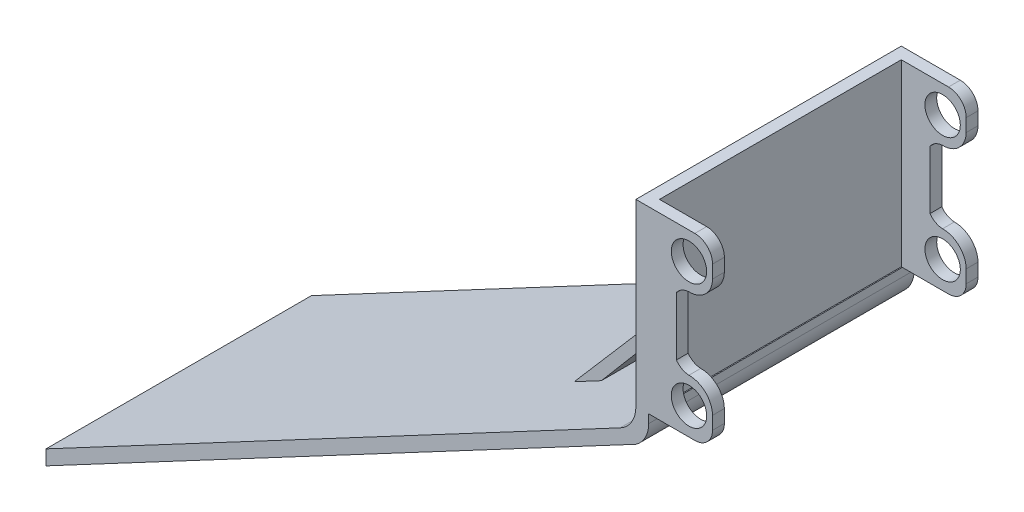
SolidWorks part; units mm, degrees
ref_plane "Plan de face" through (0, 0, 0) normal (0, 0, 1) x (1, 0, 0)
ref_plane "Plan de dessus" through (0, 0, 0) normal (0, 1, 0) x (1, 0, 0)
ref_plane "Plan de droite" through (0, 0, 0) normal (1, 0, 0) x (0, 0, -1)
sketch "Esquisse1" plane through (0, 0, 0) normal (1, 0, 0) x (0, 0, -1)
  line L0 (20.5, 0) -> (-20.5, 0)
  line L1 (-20.5, 0) -> (-20.5, -30.4)
  line L2 (-20.5, -30.4) -> (20.5, -30.4)
  line L3 (0, 9.6881) -> (0, -31.4707) construction
  line L4 (20.5, 0) -> (20.5, -30.4)
  point P8 (0, -30.4)
  point P9 (0, 0)
  dimension "D1" = 20.5
  dimension "D2" = 30.4
  dimension "D3" = 41
extrude "Boss.-Extru.1" add sketch "Esquisse1" along normal blind 2
sketch "Esquisse3" plane through (0, 0, 20.5) normal (0, 0, 1) x (1, 0, 0)
  line L0 (0, 0) -> (0, -30.4)
  line L1 (0, 0) -> (10, 0)
  line L2 (0, -30.4) -> (10, -30.4)
  line L3 (13, -3) -> (13, -5.196)
  line L4 (10, -15.2) -> (-32.1467, -15.2) construction
  line L5 (6.8684, -10.2502) -> (6.8684, -20.1498)
  line L6 (13, -25.204) -> (13, -27.4)
  circle A0 centre (9, -4.61) radius 3
  arc A1 (8.9893, -21.3235) -> (6.8684, -20.1498) centre (9.1338, -18.5593) cw
  arc A2 (13, -5.196) -> (8.9893, -9.0765) centre (9.0597, -5.1363) cw
  arc A3 (8.9893, -9.0765) -> (6.8684, -10.2502) centre (9.1338, -11.8407) ccw
  arc A4 (13, -25.204) -> (8.9893, -21.3235) centre (9.0597, -25.2637) ccw
  circle A5 centre (9, -25.79) radius 3
  arc A6 (10, 0) -> (13, -3) centre (10, -3) cw
  arc A7 (10, -30.4) -> (13, -27.4) centre (10, -27.4) ccw
  point P24 (13, 0)
  dimension "D3" = 6
  dimension "D4" = 3
  dimension "D6" = 4
  dimension "D2" = 3
  dimension "D5" = 4.61
  dimension "D1" = 13
extrude "Boss.-Extru.2" add sketch "Esquisse3" along normal blind 2
mirror "Symétrie1" about plane through (0, 0, 0) normal (0, 0, 1) of "Boss.-Extru.2"
sketch "Esquisse4" plane through (0, 0, 0) normal (-1, 0, 0) x (0, 0, 1)
  line L0 (-22.5, 0) -> (-22.5, -30.4) construction
  line L1 (-7.5, -7.5) -> (7.5, -7.5)
  line L2 (-7.5, -7.5) -> (-7.5, -22.9)
  line L3 (-7.5, -22.9) -> (7.5, -22.9)
  line L4 (7.5, -7.5) -> (7.5, -22.9)
  line L5 (22.5, 0) -> (22.5, -30.4) construction
  line L6 (-22.5, 0) -> (22.5, 0) construction
  line L7 (22.5, -30.4) -> (-22.5, -30.4) construction
  dimension "D1" = 15
  dimension "D2" = 15
  dimension "D3" = 7.5
  dimension "D4" = 7.5
extrude "Boss.-Extru.3" add sketch "Esquisse4" along normal blind 2.5
sketch "Esquisse11" plane through (0, 0, -22.5) normal (0, 0, -1) x (-1, 0, 0)
  line L0 (0, 0) -> (0, -30.4) construction
  line L1 (100, -86.6309) -> (100, -89.1309)
  line L4 (100, -89.1309) -> (0, -35.96)
  line L5 (0, -35.96) -> (0, -33.46)
  line L6 (0, -33.46) -> (100, -86.6309)
  point P2 (0, -35.96)
  dimension "D1" = 2.5
  dimension "D2" = 100
  dimension "D3" = 118
  dimension "D4" = 100
  dimension "D5" = 118
extrude "Boss.-Extru.9" add sketch "Esquisse11" against normal up to vertex (45 mm away) up to point (0, -30.4, 22.5)
sketch "Esquisse12" plane through (0, 0, -7.5) normal (0, 0, -1) x (-1, 0, 0)
  line L0 (2.5, -22.9) -> (20.8446, -44.5433)
  line L1 (100, -86.6309) -> (0, -33.46) construction
  line L2 (20.8446, -44.5433) -> (25.4455, -46.9896)
  line L3 (25.4455, -46.9896) -> (2.5, -20.4)
  line L4 (2.5, -7.5) -> (2.5, -22.9) construction
  line L5 (2.5, -20.4) -> (2.5, -22.9)
  point P5 (21.1988, -42.0685)
  dimension "D1" = 2.5
  dimension "D2" = 2.5
  dimension "D3" = 35.1213
  dimension "D4" = 139.207
extrude "Boss.-Extru.10" add sketch "Esquisse12" against normal up to vertex (15 mm away) up to point (-2.5, -22.9, 7.5)
sketch "Esquisse13" plane through (0, 0, -22.5) normal (0, 0, -1) x (-1, 0, 0)
  line L0 (0, -30.4) -> (0, -35.96)
  line L1 (0, -33.46) -> (0, -35.96) construction
  line L2 (0, -35.96) -> (-2.1725, -35.96)
  line L3 (-2.1725, -35.96) -> (-2.1725, -30.4)
  line L4 (0, -30.4) -> (-10, -30.4) construction
  line L5 (-2.1725, -30.4) -> (0, -30.4)
  line L11 (0, 0) -> (-10, 0)
  line L12 (-13, -3) -> (-13, -5.196)
  line L13 (-6.8684, -10.2502) -> (-6.8684, -20.1498)
  line L14 (-13, -25.204) -> (-13, -27.4)
  line L15 (-10, -30.4) -> (0, -30.4)
  line L16 (0, -30.4) -> (0, 0)
  line L17 (0, 0) -> (-10, 0)
  line L18 (-13, -3) -> (-13, -5.196)
  line L19 (-6.8684, -10.2502) -> (-6.8684, -20.1498)
  line L20 (-13, -25.204) -> (-13, -27.4)
  line L21 (-10, -30.4) -> (-2.1725, -30.4)
  arc A6 (-10, 0) -> (-13, -3) centre (-10, -3) ccw
  arc A7 (-13, -5.196) -> (-8.9893, -9.0765) centre (-9.0597, -5.1363) ccw
  arc A8 (-6.8684, -10.2502) -> (-8.9893, -9.0765) centre (-9.1338, -11.8407) ccw
  arc A9 (-8.9893, -21.3235) -> (-6.8684, -20.1498) centre (-9.1338, -18.5593) ccw
  arc A10 (-8.9893, -21.3235) -> (-13, -25.204) centre (-9.0597, -25.2637) ccw
  arc A11 (-13, -27.4) -> (-10, -30.4) centre (-10, -27.4) ccw
  arc A12 (-10, 0) -> (-13, -3) centre (-10, -3) ccw
  arc A13 (-13, -5.196) -> (-8.9893, -9.0765) centre (-9.0597, -5.1363) ccw
  arc A14 (-6.8684, -10.2502) -> (-8.9893, -9.0765) centre (-9.1338, -11.8407) ccw
  arc A15 (-8.9893, -21.3235) -> (-6.8684, -20.1498) centre (-9.1338, -18.5593) ccw
  arc A16 (-8.9893, -21.3235) -> (-13, -25.204) centre (-9.0597, -25.2637) ccw
  arc A17 (-13, -27.4) -> (-10, -30.4) centre (-10, -27.4) ccw
  line M25 (-10, -30.4) -> (0, -30.4)
  dimension "D1" = 0
extrude "Boss.-Extru.11" add sketch "Esquisse13" against normal blind 45 contours L3 L2 L0 M25 region at (1.0863, -33.18, -22.5)
fillet "Congé2" radius 5 1 edges at (2.1725, -35.96, 0)
fillet "Congé3" radius 5 1 edges at (0, -33.46, 0)
fillet "Congé4" radius 5 2 edges at (-2.5, -7.5, 0)
